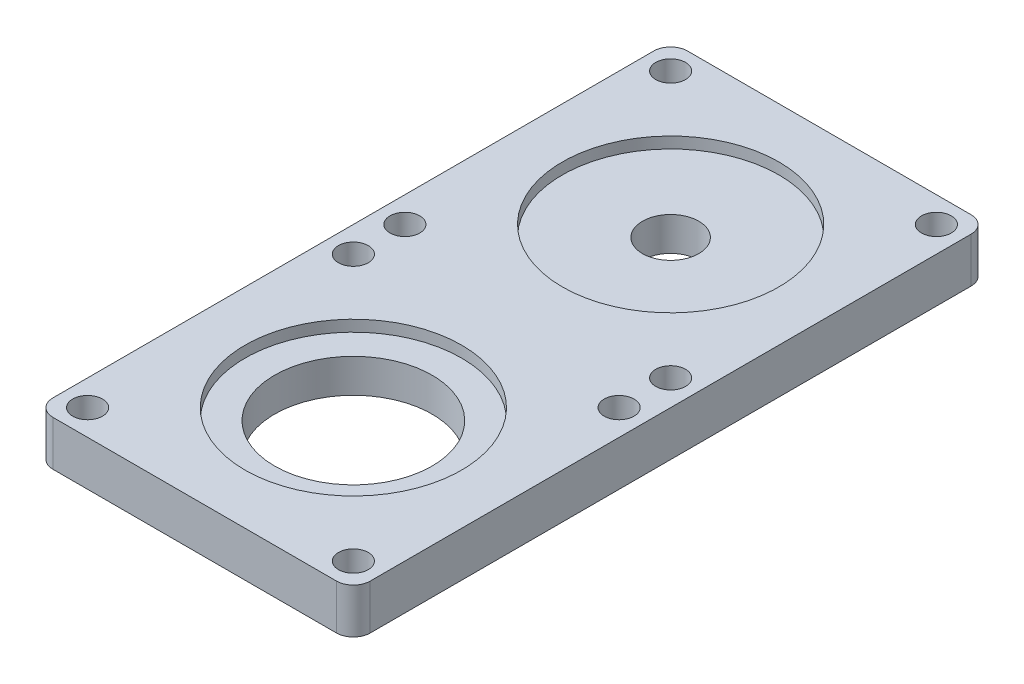
SolidWorks part; units mm, degrees
ref_plane "Front Plane" through (0, 0, 0) normal (0, 0, 1) x (1, 0, 0)
ref_plane "Top Plane" through (0, 0, 0) normal (0, 1, 0) x (1, 0, 0)
ref_plane "Right Plane" through (0, 0, 0) normal (1, 0, 0) x (0, 0, -1)
sketch "Sketch1" plane through (0, 0, 0) normal (0, 1, 0) x (1, 0, 0)
  line L0 (28.2, 0) -> (28.2, -112.8) construction
  line L1 (0, 0) -> (56.4, 0)
  line L2 (0, 0) -> (0, -112.8)
  line L3 (0, -112.8) -> (56.4, -112.8)
  line L4 (56.4, 0) -> (56.4, -112.8)
  line L5 (0, -56.4) -> (56.4, -56.4) construction
  dimension "D1" = 56.4
  dimension "D2" = 112.8
extrude "Boss-Extrude1" add sketch "Sketch1" along normal blind 8
sketch "Sketch2" plane through (0, 8, 0) normal (0, 1, 0) x (1, 0, 0)
  line L0 (0, -56.4) -> (56.4, -56.4) construction
  line L1 (0, 0) -> (0, -112.8) construction
  line L2 (56.4, -112.8) -> (56.4, 0) construction
  line L3 (28.2, 0) -> (28.2, -112.8) construction
  line L4 (56.4, 0) -> (0, 0) construction
  line L5 (0, -112.8) -> (56.4, -112.8) construction
  line L6 (0, -28.2) -> (56.4, -28.2) construction
  circle A0 centre (28.2, -28.2) radius 19.25
  dimension "D2" = 38.5
  dimension "D1" = 28.2
extrude "Cut-Extrude1" cut sketch "Sketch2" against normal blind 2
sketch "Sketch3" plane through (0, 6, 0) normal (0, 1, 0) x (1, 0, 0)
  circle A0 centre (28.2, -28.2) radius 5
  dimension "D1" = 10
extrude "Cut-Extrude2" cut sketch "Sketch3" against normal through all
sketch "Sketch4" plane through (0, 8, 0) normal (0, 1, 0) x (1, 0, 0)
  line L0 (56.4, 0) -> (0, 0) construction
  line L1 (28.2, 0) -> (28.2, -86.1901) construction
  line L2 (0, -28.2) -> (56.4, -28.2) construction
  line L3 (0, 0) -> (0, -112.8) construction
  line L4 (56.4, -112.8) -> (56.4, 0) construction
  line L5 (0, -56.4) -> (56.4, -56.4) construction
  circle A0 centre (4.58, -4.58) radius 2.65
  circle A1 centre (51.82, -4.58) radius 2.65
  circle A2 centre (51.82, -51.82) radius 2.65
  circle A3 centre (4.58, -51.82) radius 2.65
  dimension "D4" = 5.3
  dimension "D1" = 23.62
  dimension "D2" = 28.2
  dimension "D3" = 23.62
extrude "Cut-Extrude3" cut sketch "Sketch4" against normal through all
sketch "Sketch5" plane through (0, 8, 0) normal (0, 1, 0) x (1, 0, 0)
  line L0 (0, -56.4) -> (56.4, -56.4) construction
  line L1 (0, 0) -> (0, -112.8) construction
  line L2 (56.4, -112.8) -> (56.4, 0) construction
  line L3 (0, -84.6) -> (56.4, -84.6) construction
  line L4 (28.2, 0) -> (28.2, -112.8) construction
  line L5 (56.4, 0) -> (0, 0) construction
  line L6 (0, -112.8) -> (56.4, -112.8) construction
  circle A0 centre (28.2, -84.6) radius 14
  point P14 (28.2, -84.6)
  dimension "D2" = 28
  dimension "D1" = 28.2
extrude "Cut-Extrude4" cut sketch "Sketch5" against normal through all
ref_plane "Plane1" through (0, 0, 56.4) normal (0, 0, 1) x (1, 0, 0)
mirror "Mirror1" about plane through (0, 0, 56.4) normal (0, 0, 1) of "Cut-Extrude3"
mirror "Mirror2" about plane through (0, 0, 56.4) normal (0, 0, 1) of "Cut-Extrude1"
fillet "Fillet2" radius 3 4 edges at (0, 4, 0) (56.4, 4, 0) (56.4, 4, 112.8) (0, 4, 112.8)
